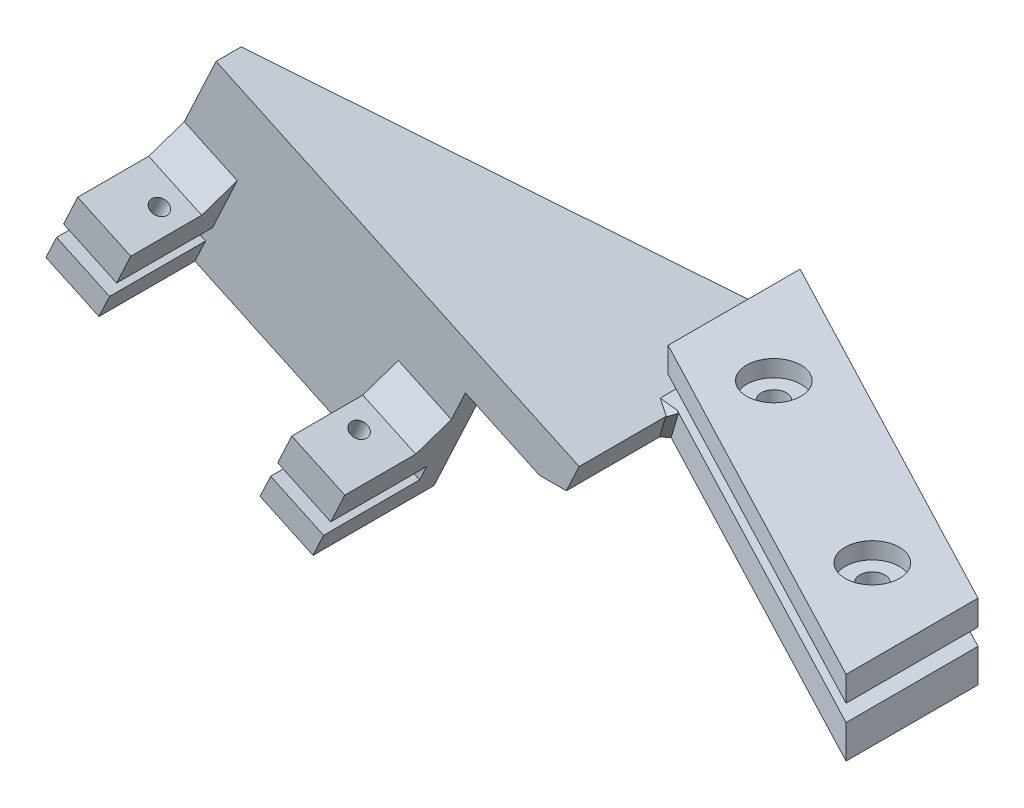
SolidWorks part; units mm, degrees
ref_plane "Front Plane" through (0, 0, 0) normal (0, 0, 1) x (1, 0, 0)
ref_plane "Top Plane" through (0, 0, 0) normal (0, 1, 0) x (1, 0, 0)
ref_plane "Right Plane" through (0, 0, 0) normal (1, 0, 0) x (0, 0, -1)
sketch "Sketch1" plane through (0, 0, 0) normal (0, 1, 0) x (1, 0, 0)
  line L0 (0, 6) -> (0, -19) construction
  line L1 (0, -19) -> (24.7992, -19) construction
  circle A0 centre (0, 0) radius 6
  circle A1 centre (24.7992, -13) radius 6
  dimension "D1" = 28
  dimension "D2" = 12
  dimension "D3" = 12
  dimension "D4" = 25
sketch "Sketch3" plane through (0, 0, 0) normal (0, 1, 0) x (1, 0, 0)
  line L0 (-10, 13.1456) -> (-10, -2.6614)
  line L1 (-10, -2.6614) -> (34.7992, -26.1456)
  line L2 (34.7992, -26.1456) -> (34.7992, -10.3386)
  line L3 (34.7992, -10.3386) -> (-10, 13.1456)
  line L5 (0, 0) -> (24.7992, -13) construction
  line L6 (0, 6) -> (0, -19) construction
  dimension "D1" = 7
  dimension "D2" = 7
  dimension "D3" = 10
  dimension "D4" = 10
extrude "Boss-Extrude1" add sketch "Sketch3" along normal blind 3
extrude "Boss-Extrude3" add sketch "Sketch1" against normal blind 2
sketch "Sketch4" plane through (0, 3, 0) normal (0, 1, 0) x (1, 0, 0)
  circle A0 centre (0, 0) radius 1.5
  circle A1 centre (24.7992, -13) radius 1.5
  dimension "D1" = 3
  dimension "D2" = 3
extrude "Cut-Extrude1" cut sketch "Sketch4" against normal through all
sketch "Sketch5" plane through (0, 3, 0) normal (0, 1, 0) x (1, 0, 0)
  circle A0 centre (0, 0) radius 3.25
  circle A1 centre (24.7992, -13) radius 3.25
  dimension "D1" = 6.5
  dimension "D2" = 6.5
extrude "Cut-Extrude2" cut sketch "Sketch5" against normal blind 2
sketch "Sketch6" plane through (0, -2, 0) normal (0, -1, 0) x (1, 0, 0)
  line L0 (-10, 2.6614) -> (-10, -13.1456)
  line L1 (-10, -13.1456) -> (34.7992, 10.3386)
  line L2 (34.7992, 10.3386) -> (34.7992, 26.1456)
  line L3 (34.7992, 26.1456) -> (-10, 2.6614)
  circle A0 centre (0, 0) radius 1.5
  circle A1 centre (24.7992, 13) radius 1.5
  circle A2 centre (24.7992, 13) radius 1.5 construction
  circle A3 centre (0, 0) radius 1.5 construction
extrude "Boss-Extrude4" add sketch "Sketch6" along normal blind 4 separate body
sketch "Sketch12" plane through (0, 0, 0) normal (0, 0, 1) x (1, 0, 0)
  line L0 (-10, -2) -> (-10, -6.5315)
  line L1 (-10, -6.5315) -> (-12.1131, -6.5315)
  line L2 (-12.1131, -6.5315) -> (-10, -2)
  line L3 (-10, -2) -> (-1.422, -6)
  line L4 (34.7992, -6) -> (-10, -6) construction
  line L5 (-10, -6.5315) -> (-11.7357, -5.7222)
  dimension "D1" = 25
  dimension "D2" = 5
ref_plane "Plane1" through (0, -6.5315, 0) normal (0, -1, 0) x (-1, 0, 0)
ref_plane "Plane2" through (-2.5521, -5.473, 0) normal (0.4226, 0.9063, 0) x (0.9063, -0.4226, 0)
sketch "Sketch19" plane through (-2.5521, -5.473, 0) normal (0.4226, 0.9063, 0) x (0.9063, -0.4226, 0)
  line L0 (-6.5274, 13.1456) -> (-6.5274, -14.8544)
  line L2 (-6.5274, -14.8544) -> (-54.5274, -14.8544)
  line L3 (-54.5274, -14.8544) -> (-54.5274, 13.1456)
  line L4 (-54.5274, 13.1456) -> (-6.5274, 13.1456)
  dimension "D1" = 48
  dimension "D2" = 28
extrude "Boss-Extrude9" add sketch "Sketch19" against normal blind 5
sketch "Sketch22" plane through (0, 0, 14.8544) normal (0, 0, 1) x (1, 0, 0)
  line L0 (-51.9707, 17.5713) -> (-60.8457, -1.4612)
  line L1 (-60.8457, -1.4612) -> (-28.853, -16.3796)
  line L2 (-28.853, -16.3796) -> (-19.978, 2.6528)
  line L3 (-51.9707, 17.5713) -> (-8.4679, -2.7144) construction
  line L4 (-19.978, 2.6528) -> (-51.9707, 17.5713)
  dimension "D1" = 21
  dimension "D2" = 35.3
extrude "Boss-Extrude10" add sketch "Sketch22" against normal blind 3
sketch "Sketch23" plane through (0, 0, 14.8544) normal (0, 0, 1) x (1, 0, 0)
  line L0 (-58.7326, 3.0703) -> (-57.0421, 6.6956)
  line L1 (-60.8457, -1.4612) -> (-51.9707, 17.5713) construction
  line L2 (-57.0421, 6.6956) -> (-50.6979, 3.7372)
  line L3 (-50.6979, 3.7372) -> (-52.3884, 0.112)
  line L4 (-52.3884, 0.112) -> (-58.7326, 3.0703)
  line L5 (-60.8457, -1.4612) -> (-59.5778, 1.2577)
  line L6 (-59.5778, 1.2577) -> (-53.2337, -1.7006)
  line L7 (-53.2337, -1.7006) -> (-54.5015, -4.4195)
  line L8 (-60.8457, -1.4612) -> (-28.853, -16.3796) construction
  line L9 (-54.5015, -4.4195) -> (-60.8457, -1.4612)
  line L10 (-44.8493, -8.9204) -> (-35.9744, 10.112) construction
  line L11 (-51.9707, 17.5713) -> (-8.4679, -2.7144) construction
  line L12 (-35.1972, -13.4213) -> (-28.853, -16.3796)
  line L13 (-33.9293, -10.7024) -> (-35.1972, -13.4213)
  line L14 (-27.5851, -13.6607) -> (-33.9293, -10.7024)
  line L15 (-28.853, -16.3796) -> (-27.5851, -13.6607)
  line L16 (-33.0841, -8.8898) -> (-26.7399, -11.8481)
  line L17 (-31.3936, -5.2645) -> (-33.0841, -8.8898)
  line L18 (-25.0494, -8.2229) -> (-31.3936, -5.2645)
  line L19 (-26.7399, -11.8481) -> (-25.0494, -8.2229)
  dimension "D1" = 4
  dimension "D2" = 7
  dimension "D3" = 3
  dimension "D4" = 2
extrude "Boss-Extrude11" add sketch "Sketch23" along normal blind 11.5
sketch "Sketch24" plane through (-11.4271, -24.5055, 0) normal (-0.4226, -0.9063, 0) x (0.9063, -0.4226, 0)
  line L0 (-47.5274, 20.6044) -> (-50.0774, 20.6044) construction
  line L1 (-47.5274, 26.3544) -> (-47.5274, 14.8544) construction
  line L2 (-36.8774, 14.8544) -> (-36.8774, 11.8544) construction
  line L3 (-47.5274, 14.8544) -> (-26.2274, 14.8544) construction
  line L4 (-19.2274, 11.8544) -> (-54.5274, 11.8544) construction
  circle A0 centre (-50.0774, 20.6044) radius 1
  circle A1 centre (-23.6774, 20.6044) radius 1
  dimension "D1" = 2.55
  dimension "D2" = 2
extrude "Cut-Extrude3" cut sketch "Sketch24" against normal through all
sketch "Sketch25" plane through (0, -6, 0) normal (0, -1, 0) x (1, 0, 0)
  line L0 (-1.7598, -8.826) -> (-0.856, -22.3434)
  line L1 (-10, -13.1456) -> (34.7992, 10.3386) construction
  line L2 (-0.856, -22.3434) -> (-19.4164, -22.3434)
  line L3 (-19.4164, -22.3434) -> (-12.5617, 28.5921)
  line L4 (-12.5617, 28.5921) -> (-0.856, 28.5921)
  line L5 (-0.856, 28.5921) -> (-1.7598, -8.826)
extrude "Cut-Extrude4" cut sketch "Sketch25" along normal through all
sketch "Sketch26" plane through (3.25, 0, -6.1998) normal (0.4643, 0, -0.8857) x (-0.8857, 0, -0.4643)
  line L0 (-2.6472, -3.4709) -> (-2.0453, -11.2945)
  line L1 (-2.0453, -11.2945) -> (36.033, -14.5224)
  line L2 (36.033, -14.5224) -> (23.9967, 7.0882)
  line L3 (23.9967, 7.0882) -> (-2.6472, -3.4709)
extrude "Cut-Extrude5" cut sketch "Sketch26" along normal through all
chamfer "Chamfer2" distance 1 angle 45 2 edges at (-9.234, -2.3572, 3.0629) (-9.234, -4.3572, 3.0629)
chamfer "Chamfer3" distance 25 distance2 48 1 edges at (-53.0272, 15.3055, -13.1456)
chamfer "Chamfer4" distance 3 angle 45 1 edges at (-38.0874, 5.5805, 11.8544)
chamfer "Chamfer5" distance 3 angle 45 2 edges at (-53.87, 5.2164, 14.8544) (-28.2215, -6.7437, 14.8544)
